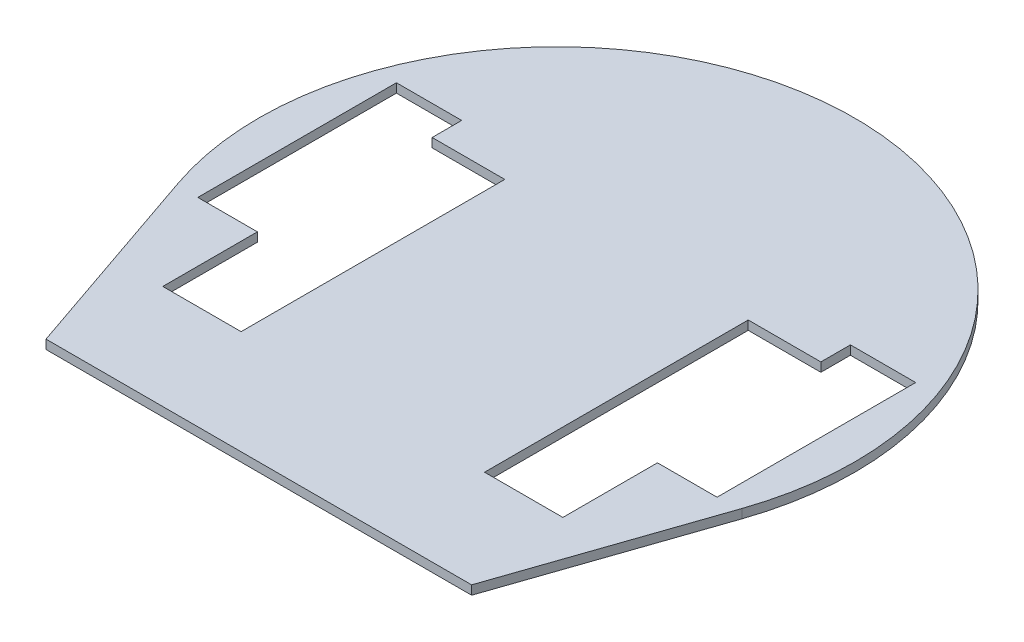
SolidWorks part; units mm, degrees
ref_plane "Front Plane" through (0, 0, 0) normal (0, 0, 1) x (1, 0, 0)
ref_plane "Top Plane" through (0, 0, 0) normal (0, 1, 0) x (1, 0, 0)
ref_plane "Right Plane" through (0, 0, 0) normal (1, 0, 0) x (0, 0, -1)
sketch "Sketch1" plane through (0, 0, 0) normal (0, 1, 0) x (1, 0, 0)
  circle A0 centre (0, 0) radius 105
  dimension "D1" = 210
extrude "Boss-Extrude1" add sketch "Sketch1" along normal blind 3.175
sketch "Sketch3" plane through (0, 0, 0) normal (0, 1, 0) x (1, 0, 0)
  line L3 (-99.3243, -34.0541) -> (-75, -105)
  line L5 (-75, -105) -> (75, -105)
  line L6 (75, -105) -> (99.3243, -34.0541)
  line L7 (99.3243, -34.0541) -> (-99.3243, -34.0541)
  circle A2 centre (0, 0) radius 105 construction
  dimension "D1" = 150
extrude "Boss-Extrude2" add sketch "Sketch3" along normal up to surface (3.175 mm away) up to face at (0, 3.175, 105)
sketch "Sketch4" plane through (0, 3.175, 0) normal (0, 1, 0) x (1, 0, 0)
  line L0 (-70, -30) -> (-70, 30) construction
  line L1 (-90, 30) -> (-90, -30) construction
  line L2 (-70, -30) -> (-70, 30) construction
  line L3 (-90, 30) -> (-90, -30) construction
  line L4 (-91.5, 35) -> (-68.5, 35)
  line L5 (-69, 19.5885) -> (-69, -54.8563) construction
  line L6 (-68.5, 35) -> (-68.5, 24.5885)
  line L7 (-44.4, 19.5885) -> (-44.4, -54.8563) construction
  line L8 (-68.5, 24.5885) -> (-42.9, 24.5885)
  line L9 (-42.9, 24.5885) -> (-42.9, -68.3372)
  line L10 (-42.9, -68.3372) -> (-70.5, -68.3372)
  line L11 (-70.5, -68.3372) -> (-70.5, -35)
  line L12 (-70.5, -35) -> (-91.5, -35)
  line L13 (-91.5, -35) -> (-91.5, 35)
  line L14 (-90, -30) -> (-90, -35) construction
  line L15 (-44.4, 24.5885) -> (-44.4, 19.5885) construction
  line L16 (-44.4, 19.5885) -> (-42.9, 19.5885) construction
  line L17 (-42.9, -54.8563) -> (-44.4, -54.8563) construction
  line L18 (-44.4, -54.8563) -> (-44.4, -68.3372) construction
  line L19 (-69, -68.3372) -> (-69, -54.8563) construction
  line L20 (-69, -54.8563) -> (-70.5, -54.8563) construction
  line L21 (-90, 35) -> (-90, 30) construction
  line L22 (-90, 30) -> (-91.5, 30) construction
  line L23 (-70, 35) -> (-70, 30) construction
  line L24 (-70, 30) -> (-68.5, 30) construction
  line L25 (0, 0) -> (0, 30.6953) construction
  line L26 (91.5, -35) -> (91.5, 35)
  line L27 (70.5, -35) -> (91.5, -35)
  line L28 (70.5, -68.3372) -> (70.5, -35)
  line L29 (42.9, -68.3372) -> (70.5, -68.3372)
  line L30 (42.9, 24.5885) -> (42.9, -68.3372)
  line L31 (68.5, 24.5885) -> (42.9, 24.5885)
  line L32 (68.5, 35) -> (68.5, 24.5885)
  line L33 (91.5, 35) -> (68.5, 35)
  line L34 (-68.9093, -68.3372) -> (-44.4907, -68.3372) construction
  dimension "D1" = 1.5
  dimension "D2" = 5
extrude "Cut-Extrude1" cut sketch "Sketch4" against normal through all
